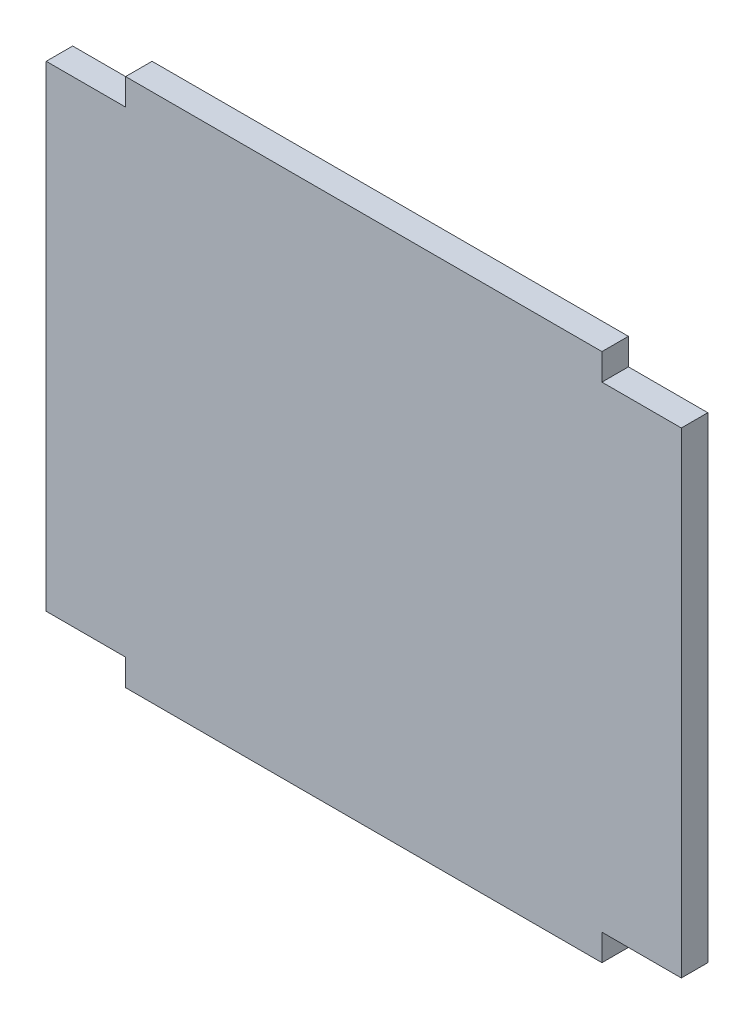
SolidWorks part; units mm, degrees
ref_plane "Front Plane" through (0, 0, 0) normal (0, 0, 1) x (1, 0, 0)
ref_plane "Top Plane" through (0, 0, 0) normal (0, 1, 0) x (1, 0, 0)
ref_plane "Right Plane" through (0, 0, 0) normal (1, 0, 0) x (0, 0, -1)
sketch "Sketch1" plane through (0, 0, 0) normal (0, 0, 1) x (1, 0, 0)
  line L1 (-38.1, -31.75) -> (38.1, -31.75)
  line L2 (-38.1, -31.75) -> (-38.1, 31.75)
  line L3 (-38.1, 31.75) -> (38.1, 31.75)
  line L4 (38.1, -31.75) -> (38.1, 31.75)
  line L5 (-38.1, -31.75) -> (38.1, 31.75) construction
  line L6 (-38.1, 31.75) -> (38.1, -31.75) construction
  point P0 (0, 0)
  dimension "D1" = 76.2
  dimension "D2" = 63.5
extrude "Boss-Extrude1" add sketch "Sketch1" along normal blind 3.175
sketch "Sketch2" plane through (0, 0, 0) normal (0, 0, -1) x (-1, 0, 0)
  line L0 (-38.1, 0) -> (38.1, 0) construction
  line L1 (-38.1, -31.75) -> (-28.575, -31.75)
  line L2 (-38.1, -31.75) -> (-38.1, -28.575)
  line L3 (-38.1, -28.575) -> (-28.575, -28.575)
  line L4 (-28.575, -31.75) -> (-28.575, -28.575)
  line L5 (38.1, -31.75) -> (28.575, -31.75)
  line L6 (38.1, -31.75) -> (38.1, -28.575)
  line L7 (38.1, -28.575) -> (28.575, -28.575)
  line L8 (28.575, -31.75) -> (28.575, -28.575)
  line L9 (-38.1, -31.75) -> (-38.1, 31.75) construction
  line L10 (38.1, 31.75) -> (38.1, -31.75) construction
  line L11 (28.575, 31.75) -> (28.575, 28.575)
  line L12 (38.1, 28.575) -> (28.575, 28.575)
  line L13 (38.1, 31.75) -> (38.1, 28.575)
  line L14 (38.1, 31.75) -> (28.575, 31.75)
  line L15 (-28.575, 31.75) -> (-28.575, 28.575)
  line L16 (-38.1, 28.575) -> (-28.575, 28.575)
  line L17 (-38.1, 31.75) -> (-38.1, 28.575)
  line L18 (-38.1, 31.75) -> (-28.575, 31.75)
  dimension "D1" = 3.175
  dimension "D2" = 57.15
extrude "Cut-Extrude1" cut sketch "Sketch2" against normal through all
